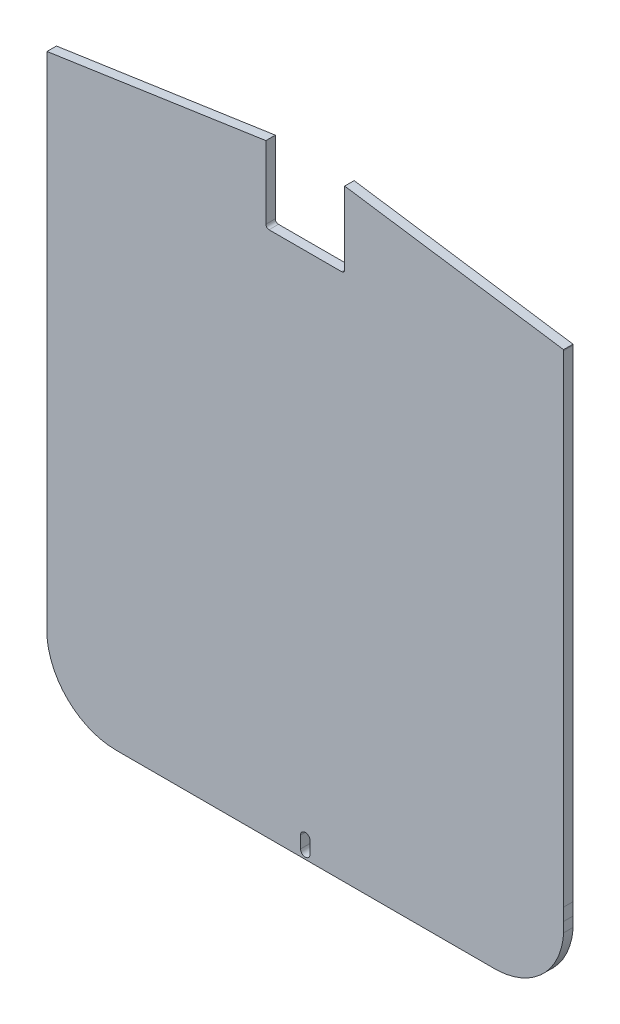
SolidWorks part; units mm, degrees
material "Beech"
ref_plane "Front Plane" through (0, 0, 0) normal (0, 0, 1) x (1, 0, 0)
ref_plane "Top Plane" through (0, 0, 0) normal (0, 1, 0) x (1, 0, 0)
ref_plane "Right Plane" through (0, 0, 0) normal (1, 0, 0) x (0, 0, -1)
sketch "Sketch1" plane through (0, 0, 0) normal (0, 0, 1) x (1, 0, 0)
  line L0 (-83, 132.5) -> (-83, -72.5)
  line L1 (-83, -72.5) -> (83, -72.5)
  line L2 (83, -72.5) -> (83, 132.5)
  line L3 (83, 132.5) -> (-83, 132.5)
  line L4 (80, -72.5) -> (80, 72.5)
  line L5 (80, 72.5) -> (-80, 72.5)
  line L6 (-80, 72.5) -> (-80, -72.5)
  line L7 (-80, -72.5) -> (80, -72.5)
  line L8 (80, -72.5) -> (80, 72.5) construction
  line L9 (80, 72.5) -> (-80, 72.5) construction
  line L10 (-80, 72.5) -> (-80, -72.5) construction
  line L11 (-80, -72.5) -> (80, -72.5) construction
  line L12 (0, 132.5) -> (0, -72.5) construction
  line L15 (0, -63.5748) -> (0, -67.368) construction
  line L16 (1.5, -63.5748) -> (1.5, -67.368)
  line L17 (-1.5, -63.5748) -> (-1.5, -67.368)
  arc A1 (1.5, -63.5748) -> (-1.5, -63.5748) centre (0, -63.5748) ccw
  arc A2 (-1.5, -67.368) -> (1.5, -67.368) centre (0, -67.368) ccw
  point P6 (0, -65.4714)
  dimension "D4" = 3
  dimension "D2" = 60
  dimension "D3" = 3
  dimension "D1" = 0
extrude "Boss-Extrude1" add sketch "Sketch1" along normal blind 3
sketch "Sketch2" plane through (0, 0, 3) normal (0, 0, 1) x (1, 0, 0)
  line L0 (82.0005, 111.3005) -> (82, -41.5853) construction
  line L1 (-82, -41.5853) -> (-82, 111.3005) construction
  line L5 (-82, -45.5285) -> (-82, -41.5853) construction
  line L9 (82, -41.5853) -> (82, -45.5236) construction
  line L11 (82.0005, 111.3005) -> (82, -41.5853)
  line L12 (-82, -41.5853) -> (-82, 111.3005)
  line L16 (-82, -45.5285) -> (-82, -41.5853)
  line L20 (82, -41.5853) -> (82, -45.5236)
  line L22 (-81.9433, 111.5318) -> (-12.5, 121.7643)
  line L23 (12.5, 121.7643) -> (81.9468, 111.5531)
  line L24 (-60, -69.5) -> (60, -69.5)
  line L26 (11.5, 122.7643) -> (-11.5, 122.7643)
  line L27 (-12.5, 121.7643) -> (-12.5, 98.7643)
  line L28 (-11.5, 97.7643) -> (11.5, 97.7643)
  line L29 (12.5, 98.7643) -> (12.5, 121.7643)
  line L31 (-12.5, 121.7643) -> (-12.5, 98.7643)
  line L32 (-11.5, 97.7643) -> (11.5, 97.7643)
  line L33 (12.5, 98.7643) -> (12.5, 121.7643)
  arc A4 (12.5, 121.7643) -> (11.5, 122.7643) centre (11.5, 121.7643) ccw
  arc A5 (-11.5, 122.7643) -> (-12.5, 121.7643) centre (-11.5, 121.7643) ccw
  arc A6 (-12.5, 98.7643) -> (-11.5, 97.7643) centre (-11.5, 98.7643) ccw
  arc A7 (11.5, 97.7643) -> (12.5, 98.7643) centre (11.5, 98.7643) ccw
  arc A10 (-12.5, 98.7643) -> (-11.5, 97.7643) centre (-11.5, 98.7643) ccw
  arc A11 (11.5, 97.7643) -> (12.5, 98.7643) centre (11.5, 98.7643) ccw
  spline S1 degree 3 poles (64.6313, 2111.4482) (75.7219, 87.3252) (81.1876, 114.41) (81.98, 111.4442) (81.9843, 111.4266) (81.9906, 111.3955) (81.9926, 111.3844) (81.9957, 111.3642) (81.9967, 111.357) (81.9981, 111.3436) (81.9986, 111.3387) (81.9994, 111.3295) (81.9996, 111.3261) (82, 111.3197) (82.0001, 111.3173) (82.0108, 111.0316) (82.3169, 104.4718) (-53.9298, -1882.3269) knots -43.429236 -43.429236 -43.429236 -43.429236 0.5 0.5 0.75 0.75 0.875 0.875 0.9375 0.9375 0.96875 0.96875 0.984375 0.984375 0.992187 0.992187 1.719046 1.719046 1.719046 1.719046 only from (81.9468, 111.5531) to (82.0005, 111.3005) construction
  spline S2 degree 3 poles (-6.3998, -1886.8401) (-82.454, 105.7484) (-82.0159, 111.0585) (-81.9992, 111.3159) (-81.9991, 111.3181) (-81.9986, 111.324) (-81.9983, 111.327) (-81.9974, 111.3354) (-81.9968, 111.3398) (-81.9951, 111.3521) (-81.994, 111.3587) (-81.9907, 111.3771) (-81.9885, 111.3872) (-81.9818, 111.4157) (-81.9773, 111.4319) (-81.1325, 114.2376) (-76.1096, 88.1744) (-11.9978, 2110.2849) knots -0.711521 -0.711521 -0.711521 -0.711521 0.007812 0.007812 0.015625 0.015625 0.03125 0.03125 0.0625 0.0625 0.125 0.125 0.25 0.25 0.5 0.5 45.844828 45.844828 45.844828 45.844828 only from (-82, 111.3005) to (-81.9433, 111.5318) construction
  spline S6 degree 3 poles (-1928.5419, -753.6745) (63.6117, 275.6443) (7.9382, -81.9801) (-64.5167, -69.0415) (-65.1695, -68.8945) (-66.4624, -68.5401) (-67.1019, -68.3331) (-68.9962, -67.6218) (-70.2266, -67.0281) (-72.0082, -65.9468) (-72.5916, -65.5539) (-73.7138, -64.7169) (-74.2553, -64.2714) (-75.8198, -62.853) (-76.7839, -61.7987) (-78.0962, -60.0325) (-78.5049, -59.4213) (-79.2649, -58.1495) (-79.6163, -57.4891) (-80.2606, -56.1075) (-80.5544, -55.3821) (-80.9352, -54.2729) (-81.0527, -53.8984) (-81.2689, -53.1383) (-81.3673, -52.7524) (-81.4958, -52.1871) (-81.5357, -52.0001) (-81.6098, -51.6297) (-81.6441, -51.4452) (-81.7371, -50.9102) (-81.7862, -50.5758) (-81.8457, -50.1062) (-81.8631, -49.9545) (-81.8935, -49.6674) (-81.9064, -49.5311) (-83.4748, -31.4486) (-53.1191, -131.2669) (-841.5879, 1801.2869) knots -6.787703 -6.787703 -6.787703 -6.787703 0.125 0.125 0.1875 0.1875 0.25 0.25 0.375 0.375 0.4375 0.4375 0.5 0.5 0.625 0.625 0.6875 0.6875 0.75 0.75 0.8125 0.8125 0.84375 0.84375 0.875 0.875 0.890625 0.890625 0.90625 0.90625 0.9375 0.9375 0.953125 0.953125 0.96875 0.96875 3.124793 3.124793 3.124793 3.124793 only from (-60, -69.5) to (-81.9679, -48.688) construction
  spline S7 degree 3 poles (-13.4948, -2047.5013) (-136.3888, 1835.3213) (-39.6188, -1934.0133) (-114.2264, 1954.123) knots -28.339841 -28.339841 -28.339841 -28.339841 28.343891 28.343891 28.343891 28.343891 only from (-81.9679, -48.688) to (-82, -45.5285) construction
  spline S8 degree 3 poles (794.697, 1819.9789) (54.8376, -129.8237) (83.4208, -32.1012) (81.8945, -49.6678) (81.865, -49.9542) (81.7857, -50.579) (81.7351, -50.9226) (81.6112, -51.6337) (81.5376, -52.0037) (81.3638, -52.7669) (81.1692, -53.5272) (80.933, -54.2797) (80.5472, -55.4017) (80.2557, -56.1194) (79.7684, -57.1621) (79.5972, -57.5046) (79.2419, -58.172) (79.0574, -58.4979) (78.4837, -59.4543) (78.0743, -60.0639) (77.2026, -61.2333) (76.7393, -61.7941) (75.7636, -62.8633) (75.2571, -63.3657) (73.6849, -64.7834) (72.567, -65.6101) (70.7961, -66.6813) (70.1901, -67.0099) (69.2586, -67.4599) (68.9441, -67.6027) (68.3147, -67.8711) (67.999, -67.9971) (66.4157, -68.5871) (65.1346, -68.9322) (-8.5713, -82.034) (-91.5091, 277.2389) (2042.4691, -25.5436) knots -2.020062 -2.020062 -2.020062 -2.020062 0.03125 0.03125 0.0625 0.0625 0.09375 0.09375 0.125 0.125 0.15625 0.1875 0.1875 0.25 0.25 0.28125 0.28125 0.3125 0.3125 0.375 0.375 0.4375 0.4375 0.5 0.5 0.625 0.625 0.6875 0.6875 0.71875 0.71875 0.75 0.75 0.875 0.875 7.923893 7.923893 7.923893 7.923893 only from (81.968, -48.6859) to (60, -69.5) construction
  spline S11 degree 3 poles (115.3198, 1954.1209) (38.1469, -1931.6616) (138.3006, 1832.75) (11.0739, -2047.3422) knots -27.882069 -27.882069 -27.882069 -27.882069 29.920199 29.920199 29.920199 29.920199 only from (82, -45.5236) to (81.968, -48.6859) construction
  spline S13 degree 3 poles (81.9468, 111.5531) (81.957, 111.5243) (81.9665, 111.4946) (81.98, 111.4442) (81.9843, 111.4266) (81.9906, 111.3955) (81.9926, 111.3844) (81.9957, 111.3642) (81.9967, 111.357) (81.9981, 111.3436) (81.9986, 111.3387) (81.9994, 111.3295) (81.9996, 111.3261) (82, 111.3197) (82.0001, 111.3173) (82.0003, 111.3112) (82.0005, 111.3075) (82.0005, 111.3005) knots 0 0 0 0 0.5 0.5 0.75 0.75 0.875 0.875 0.9375 0.9375 0.96875 0.96875 0.984375 0.984375 0.992187 0.992187 1 1 1 1
  spline S14 degree 3 poles (-82, 111.3005) (-81.9998, 111.307) (-81.9996, 111.3104) (-81.9992, 111.3159) (-81.9991, 111.3181) (-81.9986, 111.324) (-81.9983, 111.327) (-81.9974, 111.3354) (-81.9968, 111.3398) (-81.9951, 111.3521) (-81.994, 111.3587) (-81.9907, 111.3771) (-81.9885, 111.3872) (-81.9818, 111.4157) (-81.9773, 111.4319) (-81.9634, 111.478) (-81.9537, 111.5053) (-81.9433, 111.5318) knots 0 0 0 0 0.007812 0.007812 0.015625 0.015625 0.03125 0.03125 0.0625 0.0625 0.125 0.125 0.25 0.25 0.5 0.5 1 1 1 1
  spline S18 degree 3 poles (-60, -69.5) (-61.2759, -69.5) (-62.569, -69.3893) (-64.5167, -69.0415) (-65.1695, -68.8945) (-66.4624, -68.5401) (-67.1019, -68.3331) (-68.9962, -67.6218) (-70.2266, -67.0281) (-72.0082, -65.9468) (-72.5916, -65.5539) (-73.7138, -64.7169) (-74.2553, -64.2714) (-75.8198, -62.853) (-76.7839, -61.7987) (-78.0962, -60.0325) (-78.5049, -59.4213) (-79.2649, -58.1495) (-79.6163, -57.4891) (-80.2606, -56.1075) (-80.5544, -55.3821) (-80.9352, -54.2729) (-81.0527, -53.8984) (-81.2689, -53.1383) (-81.3673, -52.7524) (-81.4958, -52.1871) (-81.5357, -52.0001) (-81.6098, -51.6297) (-81.6441, -51.4452) (-81.7371, -50.9102) (-81.7862, -50.5758) (-81.8457, -50.1062) (-81.8631, -49.9545) (-81.8935, -49.6674) (-81.9064, -49.5311) (-81.9403, -49.1408) (-81.9561, -48.9053) (-81.9679, -48.688) knots 0 0 0 0 0.125 0.125 0.1875 0.1875 0.25 0.25 0.375 0.375 0.4375 0.4375 0.5 0.5 0.625 0.625 0.6875 0.6875 0.75 0.75 0.8125 0.8125 0.84375 0.84375 0.875 0.875 0.890625 0.890625 0.90625 0.90625 0.9375 0.9375 0.953125 0.953125 0.96875 0.96875 1 1 1 1
  spline S19 degree 3 poles (-81.9679, -48.688) (-81.9854, -47.6635) (-81.9954, -46.6384) (-82, -45.5285) knots 0 0 0 0 1 1 1 1
  spline S20 degree 3 poles (81.968, -48.6859) (81.9563, -48.9037) (81.9403, -49.1406) (81.8945, -49.6678) (81.865, -49.9542) (81.7857, -50.579) (81.7351, -50.9226) (81.6112, -51.6337) (81.5376, -52.0037) (81.3638, -52.7669) (81.1692, -53.5272) (80.933, -54.2797) (80.5472, -55.4017) (80.2557, -56.1194) (79.7684, -57.1621) (79.5972, -57.5046) (79.2419, -58.172) (79.0574, -58.4979) (78.4837, -59.4543) (78.0743, -60.0639) (77.2026, -61.2333) (76.7393, -61.7941) (75.7636, -62.8633) (75.2571, -63.3657) (73.6849, -64.7834) (72.567, -65.6101) (70.7961, -66.6813) (70.1901, -67.0099) (69.2586, -67.4599) (68.9441, -67.6027) (68.3147, -67.8711) (67.999, -67.9971) (66.4157, -68.5871) (65.1346, -68.9322) (62.566, -69.3887) (61.2785, -69.5) (60, -69.5) knots 0 0 0 0 0.03125 0.03125 0.0625 0.0625 0.09375 0.09375 0.125 0.125 0.15625 0.1875 0.1875 0.25 0.25 0.28125 0.28125 0.3125 0.3125 0.375 0.375 0.4375 0.4375 0.5 0.5 0.625 0.625 0.6875 0.6875 0.71875 0.71875 0.75 0.75 0.875 0.875 1 1 1 1
  spline S23 degree 3 poles (82, -45.5236) (81.9954, -46.6329) (81.9854, -47.6606) (81.968, -48.6859) knots 0 0 0 0 1 1 1 1
  dimension "D1" = 0
extrude "Cut-Extrude1" cut sketch "Sketch2" against normal through all both and the other way through all flip side to cut
